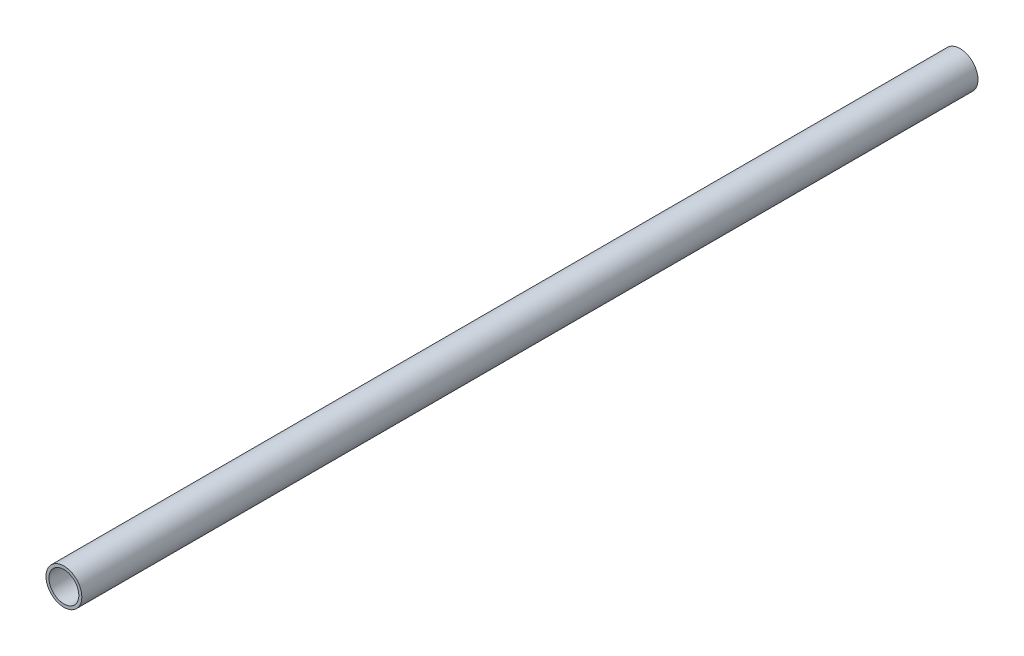
SolidWorks part; units mm, degrees
ref_plane "前视基准面" through (0, 0, 0) normal (0, 0, 1) x (1, 0, 0)
ref_plane "上视基准面" through (0, 0, 0) normal (0, 1, 0) x (1, 0, 0)
ref_plane "右视基准面" through (0, 0, 0) normal (1, 0, 0) x (0, 0, -1)
sketch "草图1" plane through (0, 0, 0) normal (0, 0, 1) x (1, 0, 0)
  circle A0 centre (0, 0) radius 6
extrude "凸台-拉伸1" add sketch "草图1" along normal blind 300
sketch "草图2" plane through (0, 0, 0) normal (0, 0, -1) x (-1, 0, 0)
  circle A0 centre (0, 0) radius 5
extrude "切除-拉伸1" cut sketch "草图2" against normal blind 300 contours A0
